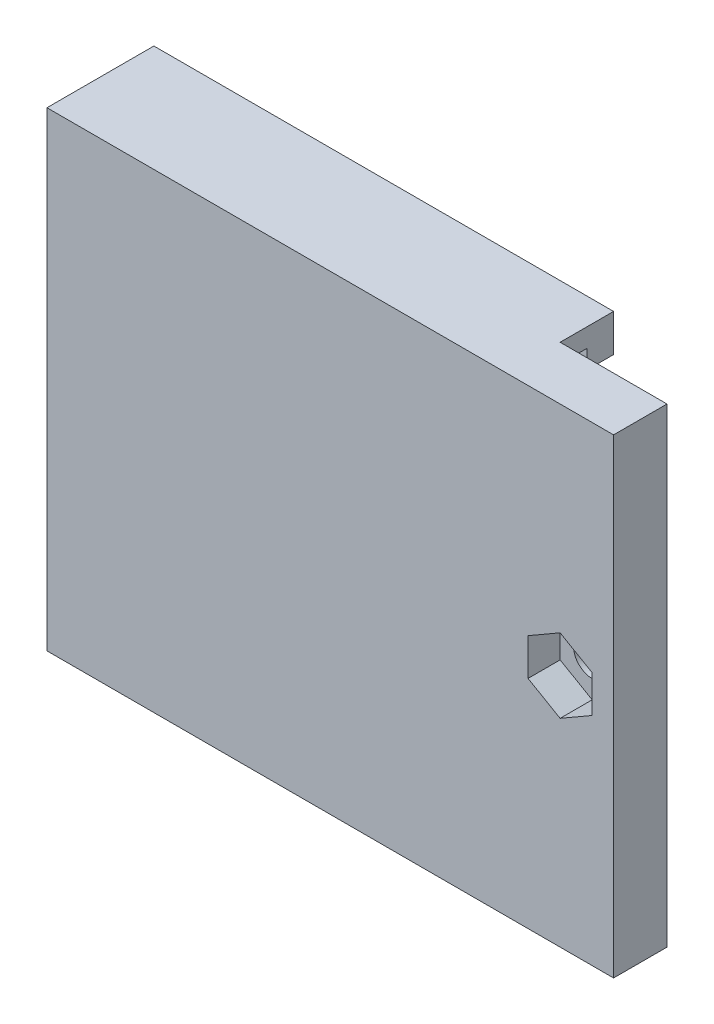
SolidWorks part; units mm, degrees
ref_plane "Alzado" through (0, 0, 0) normal (0, 0, 1) x (1, 0, 0)
ref_plane "Planta" through (0, 0, 0) normal (0, 1, 0) x (1, 0, 0)
ref_plane "Vista lateral" through (0, 0, 0) normal (1, 0, 0) x (0, 0, -1)
sketch "Croquis1" plane through (0, 0, 0) normal (0, 0, 1) x (1, 0, 0)
  line L1 (-26.5, 22) -> (26.5, 22)
  line L2 (-26.5, 22) -> (-26.5, -22)
  line L3 (-26.5, -22) -> (26.5, -22)
  line L4 (26.5, 22) -> (26.5, -22)
  line L5 (-26.5, 22) -> (26.5, -22) construction
  line L6 (-26.5, -22) -> (26.5, 22) construction
  circle A0 centre (21.5, 0) radius 1.75
  point P0 (0, 0)
  point P8 (0, 0)
  dimension "D4" = 3.5
  dimension "D1" = 44
  dimension "D2" = 53
  dimension "D3" = 5
extrude "Saliente-Extruir1" add sketch "Croquis1" along normal blind 5
sketch "Croquis2" plane through (0, 0, 5) normal (0, 0, 1) x (1, 0, 0)
  line L1 (21.5, -3.4641) -> (24.5, -1.7321)
  line L2 (24.5, -1.7321) -> (24.5, 1.7321)
  line L3 (24.5, 1.7321) -> (21.5, 3.4641)
  line L4 (21.5, 3.4641) -> (18.5, 1.7321)
  line L5 (18.5, 1.7321) -> (18.5, -1.7321)
  line L6 (18.5, -1.7321) -> (21.5, -3.4641)
  circle A0 centre (21.5, 0) radius 3 construction
  circle A1 centre (21.5, 0) radius 1.75 construction
  point P11 (0, 0)
  dimension "D1" = 6
extrude "Cortar-Extruir1" cut sketch "Croquis2" against normal blind 3
sketch "Croquis3" plane through (0, 0, 0) normal (0, 0, -1) x (-1, 0, 0)
  line L0 (-16.5, -22) -> (-16.5, -20.25)
  line L1 (26.5, -22) -> (-26.5, -22) construction
  line L2 (-16.5, -20.25) -> (26.5, -20.25)
  line L3 (26.5, 22) -> (26.5, -22) construction
  line L4 (26.5, -20.25) -> (26.5, -22)
  line L5 (26.5, -22) -> (-16.5, -22)
  line L6 (-26.5, -22) -> (-26.5, 22) construction
  line L7 (26.5, 22) -> (-16.5, 22)
  line L8 (-26.5, 22) -> (26.5, 22) construction
  line L9 (-16.5, 22) -> (-16.5, 20.25)
  line L10 (-16.5, 20.25) -> (26.5, 20.25)
  line L11 (26.5, 20.25) -> (26.5, 22)
  point P16 (0, 0)
  dimension "D1" = 10
  dimension "D2" = 1.75
extrude "Saliente-Extruir2" add sketch "Croquis3" along normal blind 5
sketch "Croquis4" plane through (0, 0, -5) normal (0, 0, -1) x (-1, 0, 0)
  line L0 (-16.5, -20.25) -> (26.5, -20.25)
  line L1 (26.5, -20.25) -> (26.5, -18.5)
  line L2 (26.5, 20.25) -> (26.5, -20.25) construction
  line L3 (26.5, -18.5) -> (-16.5, -18.5)
  line L4 (-16.5, -18.5) -> (-16.5, -20.25)
  line L5 (-16.5, 20.25) -> (-16.5, 18.5)
  line L6 (-16.5, 18.5) -> (26.5, 18.5)
  line L7 (26.5, 18.5) -> (26.5, 20.25)
  line L8 (26.5, 20.25) -> (-16.5, 20.25)
  dimension "D1" = 1.75
  dimension "D2" = 1.75
extrude "Saliente-Extruir3" add sketch "Croquis4" against normal blind 2.5
sketch "Croquis5" plane through (0, 0, 0) normal (0, 0, -1) x (-1, 0, 0)
  line L0 (26.5, -4) -> (26.5, 4)
  line L1 (26.5, 20.25) -> (26.5, -20.25) construction
  line L2 (26.5, -4) -> (19, -4)
  line L3 (19, -4) -> (19, 4)
  line L4 (19, 4) -> (26.5, 4)
  point P4 (26.5, 0)
  dimension "D1" = 8
  dimension "D2" = 7.5
extrude "Cortar-Extruir2" cut sketch "Croquis5" against normal blind 1.5
